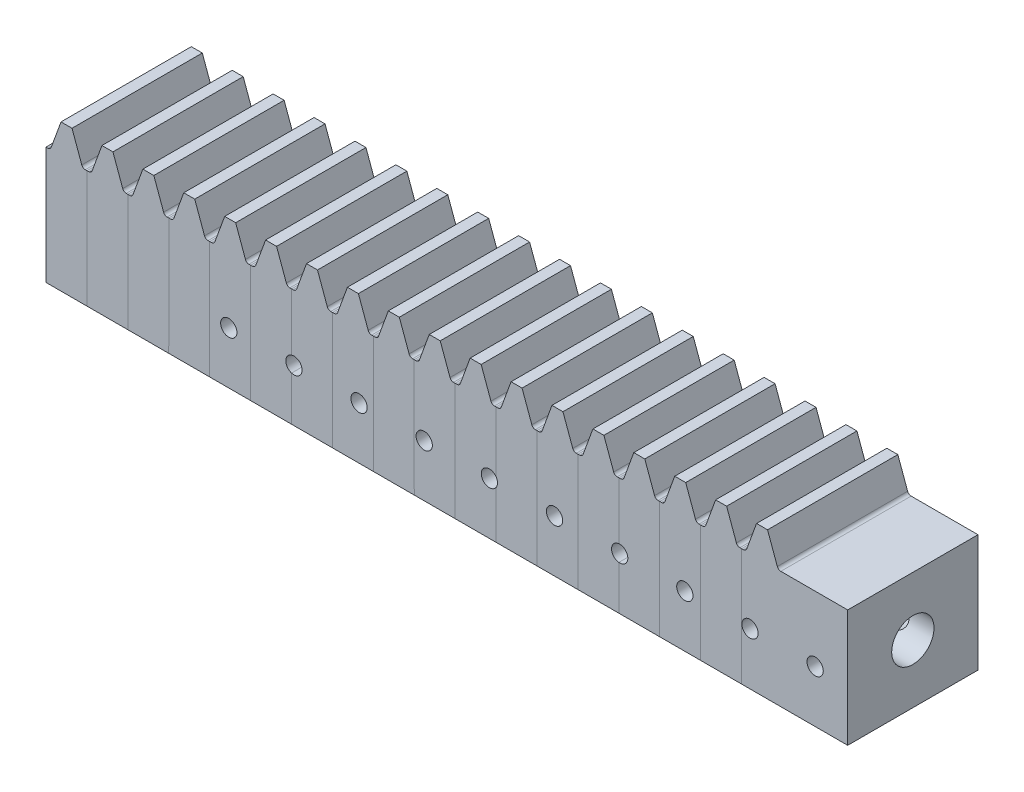
SolidWorks part; units mm, degrees
note: '?' marks a value the reader was unsure of.
ref_plane "Front Plane" through (0, 0, 0) normal (0, 0, 1) x (1, 0, 0)
ref_plane "Top Plane" through (0, 0, 0) normal (0, 1, 0) x (1, 0, 0)
ref_plane "Right Plane" through (0, 0, 0) normal (1, 0, 0) x (0, 0, -1)
ref_axis "Axis1" through (0.1856, 0, 0) along (-1, 0, 0)?
sketch "Sketch1" plane through (0, 0, 0) normal (0, 0, 1) x (1, 0, 0)
  line L0 (-4.9614, 0) -> (-3.3236, 4.5)
  line L1 (-3.3236, 4.5) -> (-1.6379, 4.5)
  line L2 (-1.6379, 4.5) -> (0, 0)
  line L3 (-4.9614, 0) -> (-6.2832, 0) construction
  line L4 (-4.9614, 0) -> (0, 0)
  line L5 (-4.7795, 0.5) -> (-6.4652, 0.5) construction
  line L6 (-6.2832, 0) -> (-7.1931, 2.5) construction
  line L7 (-7.1931, 2.5) -> (-0.9099, 2.5) construction
  dimension "D1" = 2
  dimension "D2" = 4.5
  dimension "D3" = 6.2832
  dimension "D4" = 4
  dimension "D5" = 70
  dimension "D6" = 1.3217
  dimension "D7" = 4.9614
extrude "Main" add sketch "Sketch1" along normal blind 20
ref_plane "HolePlan" through (-20, 0, 0) normal (1, 0, 0) x (0, 0, -1)
sketch "Sketch2" plane through (0, 0, 20) normal (0, 0, 1) x (1, 0, 0)
  line L1 (-5.6284, 0) -> (0.667, 0)
  line L2 (-5.6284, 0) -> (-5.6284, -18)
  line L3 (-5.6284, -18) -> (0.667, -18)
  line L4 (0.667, 0) -> (0.667, -18)
  line L6 (0.1856, 0) -> (-3.898, 0) construction
  point P12 (0, 0)
  dimension "D1" = 18
  dimension "D2" = 0.667
  dimension "D3" = 0.667
extrude "Support" add sketch "Sketch2" against normal up to surface (20 mm away) up to face at (-2.4807, 2.25, 0)
fillet "Fillet1" radius 0.57 2 edges at (-4.9614, 0, 10) (0, 0, 10)
pattern_linear "LPattern2" count 18 spacing 6.28 along (-1, 0, 0) of bodies 111 112
sketch "Sketch3" plane through (-20, 0, 0) normal (-1, 0, 0) x (0, 0, 1)
  line L0 (0, -18) -> (20, -18) construction
  line L1 (20, 0) -> (20, -18) construction
  circle A0 centre (10, -9) radius 6.15
  point P2 (10, -18)
  point P3 (20, -9)
  dimension "D1" = 12.3
extrude "AxisHole" cut sketch "Sketch3" along normal through all
sketch "Sketch4" plane through (0.667, 0, 0) normal (1, 0, 0) x (0, 0, -1)
  line L0 (0, -18) -> (-20, -18) construction
  line L1 (-20, -18) -> (0, -18)
  line L2 (-20, -18) -> (-20, 0)
  line L3 (-20, 0) -> (0, 0)
  line L4 (0, -18) -> (0, 0)
  line L5 (-20, 0) -> (0, 0) construction
  line L6 (0, 0) -> (-20, 0) construction
  line L7 (-20, -18) -> (-20, 0) construction
  line L8 (0, 0) -> (-20, 0) construction
  line L9 (-10, 0) -> (-10, -18) construction
  point P14 (-10, 0)
  dimension "D2" = 20
extrude "Boss-Extrude1" add sketch "Sketch4" along normal blind 10
sketch "Sketch5" plane through (0, 0, 20) normal (0, 0, 1) x (1, 0, 0)
  line L0 (10.667, -18) -> (-5.6284, -18) construction
  line L1 (10.667, 0) -> (10.667, -18) construction
  circle A0 centre (5.667, -10) radius 1.25
  dimension "D1" = 8
  dimension "D2" = 2.5
  dimension "D3" = 5
extrude "Cut-Extrude1" cut sketch "Sketch5" against normal through all
pattern_linear "LPattern3" count 10 spacing 10 along (-1, 0, 0) of "Cut-Extrude1"
sketch "Sketch6" plane through (-20, 0, 0) normal (-1, 0, 0) x (0, 0, 1)
  circle A0 centre (10, -9) radius 3.25
  circle A1 centre (10, -9) radius 6.15 construction
  dimension "D1" = 6.5
extrude "Cut-Extrude2" cut sketch "Sketch6" against normal through all
